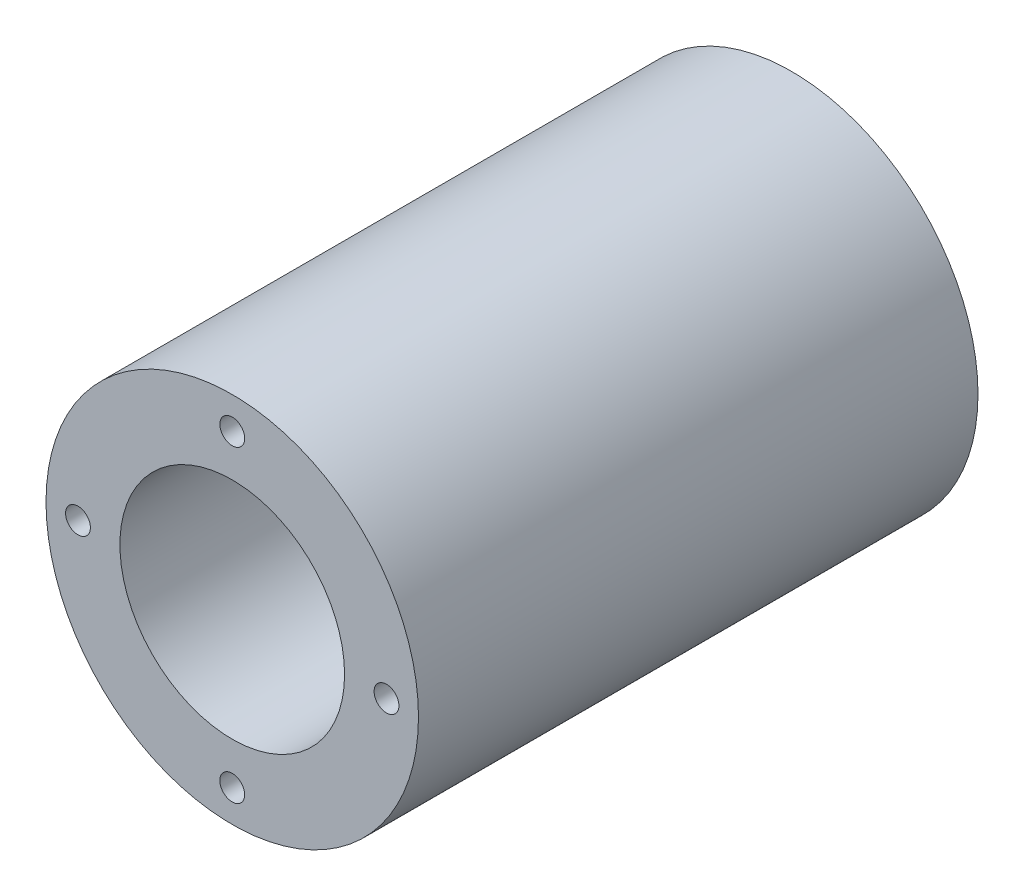
SolidWorks part; units mm, degrees
material "6061-T6 (SS)"
ref_plane "Front Plane" through (0, 0, 0) normal (0, 0, 1) x (1, 0, 0)
ref_plane "Top Plane" through (0, 0, 0) normal (0, 1, 0) x (1, 0, 0)
ref_plane "Right Plane" through (0, 0, 0) normal (1, 0, 0) x (0, 0, -1)
sketch "Sketch Spindle Skeleton" plane through (0, 0, 0) normal (1, 0, 0) x (0, 0, -1)
  line L0 (-108, -9.5) -> (-149, -9.5)
  line L5 (-1000, 0) -> (49000, 0)
  line L6 (0, -9.5) -> (0, 9.5)
  line L13 (0, 9.5) -> (-46.4, 9.5)
  line L26 (-46.4, 9.5) -> (-46.4, 14)
  line L27 (-46.4, 14) -> (-108, 14)
  line L32 (-108, 14) -> (-108, 9.5)
  line L34 (-165, 7) -> (-165, -7)
  line L36 (-108, -9.5) -> (-108, -14)
  line L37 (-108, -14) -> (-46.4, -14)
  line L38 (-46.4, -14) -> (-46.4, -9.5)
  line L39 (0, -9.5) -> (-46.4, -9.5)
  line L40 (-22.625, 37.5) -> (-13.625, 37.5)
  line L41 (-124.6, 22.6187) -> (-108, 22.6187)
  line L42 (-124.6, 22.6187) -> (-124.6, -22.6187)
  line L43 (-124.6, -22.6187) -> (-108, -22.6187)
  line L44 (-108, 22.6187) -> (-108, -22.6187)
  line L45 (-124.6, 22.6187) -> (-108, -22.6187) construction
  line L46 (-124.6, -22.6187) -> (-108, 22.6187) construction
  line L47 (-29.8, 22.6187) -> (-46.4, 22.6187)
  line L48 (-29.8, 22.6187) -> (-29.8, -22.6187)
  line L49 (-29.8, -22.6187) -> (-46.4, -22.6187)
  line L50 (-46.4, 22.6187) -> (-46.4, -22.6187)
  line L51 (-29.8, 22.6187) -> (-46.4, -22.6187) construction
  line L52 (-29.8, -22.6187) -> (-46.4, 22.6187) construction
  line L59 (-13.625, 37.5) -> (-13.625, -37.5)
  line L60 (-13.625, -37.5) -> (-22.625, -37.5)
  line L61 (-22.625, -22.6187) -> (-26.625, -22.6187)
  line L62 (-26.625, -22.6187) -> (-26.625, -12.5)
  line L63 (-26.625, -12.5) -> (-22.625, -12.5)
  line L64 (-22.625, -12.5) -> (-22.625, 12.5)
  line L65 (-22.625, 12.5) -> (-26.625, 12.5)
  line L66 (-26.625, 12.5) -> (-26.625, 22.6187)
  line L67 (-26.625, 22.6187) -> (-22.625, 22.6187)
  line L68 (-22.625, 22.6187) -> (-22.625, 37.5)
  line L69 (-22.625, -22.6187) -> (-22.625, -37.5)
  line L71 (-136.284, 37.5) -> (-23.625, 37.5)
  line L72 (-136.284, 37.5) -> (-136.284, -37.5)
  line L73 (-136.284, -37.5) -> (-23.625, -37.5)
  line L74 (-23.625, 37.5) -> (-23.625, -37.5)
  line L75 (-136.284, 37.5) -> (-23.625, -37.5) construction
  line L76 (-136.284, -37.5) -> (-23.625, 37.5) construction
  line L77 (-149, -9.5) -> (-149, -7)
  line L78 (-149, -7) -> (-165, -7)
  line L79 (-108, 9.5) -> (-149, 9.5)
  line L80 (-149, 7) -> (-165, 7)
  line L81 (-149, 9.5) -> (-149, 7)
  line L82 (-128.5, 9.5) -> (-128.5, -9.5) construction
  line L83 (-23.2, 9.5) -> (-23.2, -9.5) construction
  line L96 (-136.284, 37.5) -> (-145.284, 37.5)
  line L98 (-136.284, -37.5) -> (-145.284, -37.5)
  line L99 (-145.284, 37.5) -> (-145.284, -37.5)
  line L110 (-136.284, 37.5) -> (-136.284, -37.5)
  point P3 (0, 0)
  point P18 (-116.3, 0)
  point P24 (-38.1, 0)
  point P29 (-79.9545, 0)
  point P48 (-13.625, 31.0593)
  point P70 (-145.284, 31.0593)
sketch "Sketch1" plane through (0, 0, 0) normal (1, 0, 0) x (0, 0, -1)
  line L0 (-23.625, 37.5) -> (-23.625, -37.5) construction
  line L1 (-136.284, -37.5) -> (-23.625, -37.5) construction
  line L2 (-136.284, 37.5) -> (-136.284, -37.5) construction
  line L3 (-136.284, 37.5) -> (-23.625, 37.5) construction
  line L4 (-23.625, 37.5) -> (-23.625, -37.5)
  line L5 (-136.284, -37.5) -> (-23.625, -37.5)
  line L6 (-136.284, 37.5) -> (-136.284, -37.5)
  line L7 (-136.284, 37.5) -> (-23.625, 37.5)
  line L9 (-29.8, 22.6187) -> (-46.4, 22.6187) construction
  line L10 (-136.284, 22.6187) -> (-23.625, 22.6187)
  line L15 (-136.284, 0) -> (-23.625, 0) construction
revolve "Revolve1" add sketch "Sketch1" angle 360 about L15 region at (0, 30.0593, 79.9545)
sketch "Back Hole Top Location" plane through (0, 0, 23.625) normal (0, 0, -1) x (-1, 0, 0)
  point P9 (0, 31.0593)
hole_wizard "M6x1.0 Tapped Hole3" positions "Sketch8" profile "Sketch9" tap size "M6x1.0" standard "ANSI Metric"
sketch "Sketch8" plane through (0, 0, 23.625) normal (0, 0, -1) x (-1, 0, 0)
  point P0 (0, 31.0593)
sketch "Sketch9" plane through (0, 31.0593, 23.625) normal (1, 0, 0) x (0, 1, 0)
  line L0 (0, 0) -> (0, 16.5022)
  line L1 (0, 16.5022) -> (2.5, 15)
  line L2 (2.5, 15) -> (2.5, 0)
  line L5 (2.5, 0) -> (0, 0)
  line L10 (0, 16.5022) -> (-2.5, 15) construction
  line L11 (0, -6.35) -> (0, 107.95) construction
  dimension "Tap Drill Dia." = 5
  dimension "Tap Drill Depth" = 15
  dimension "Drill Angle" = 118
pattern_circular "BackFacePattern" count 6 over 360 about axis through (0, 0, 1000) along (0, 0, -1) of "M6x1.0 Tapped Hole3"
ref_plane "Midplane" through (0, 0, 79.9545) normal (0, 0, -1) x (-1, 0, 0)
sketch "Front Hole Top Location" plane through (0, 0, 136.284) normal (0, 0, 1) x (1, 0, 0)
  point P0 (0, 31.0593)
hole_wizard "M6x1.0 Tapped Hole2" positions "Sketch5" profile "Sketch6" tap size "M6x1.0" standard "ANSI Metric"
sketch "Sketch5" plane through (0, 0, 136.284) normal (0, 0, 1) x (1, 0, 0)
  point P0 (0, 31.0593)
sketch "Sketch6" plane through (0, 31.0593, 136.284) normal (1, 0, 0) x (0, -1, 0)
  line L0 (0, 0) -> (0, 16.5022)
  line L1 (0, 16.5022) -> (2.5, 15)
  line L2 (2.5, 15) -> (2.5, 0)
  line L5 (2.5, 0) -> (0, 0)
  line L10 (0, 16.5022) -> (-2.5, 15) construction
  line L11 (0, -6.35) -> (0, 107.95) construction
  dimension "Tap Drill Dia." = 5
  dimension "Tap Drill Depth" = 15
  dimension "Drill Angle" = 118
pattern_circular "FrontFacePattern" count 4 over 360 about axis through (0, 0, 1000) along (0, 0, -1) of "M6x1.0 Tapped Hole2"
sketch "Sketch7" plane through (0, 0, 23.625) normal (0, 0, -1) x (-1, 0, 0)
  circle A0 centre (0, 0) radius 26.9875
  circle A1 centre (0, 0) radius 24.6062
  dimension "D1" = 53.975
  dimension "D2" = 49.2125
extrude "Cut-Extrude1" cut sketch "Sketch7" against normal blind 0.5
